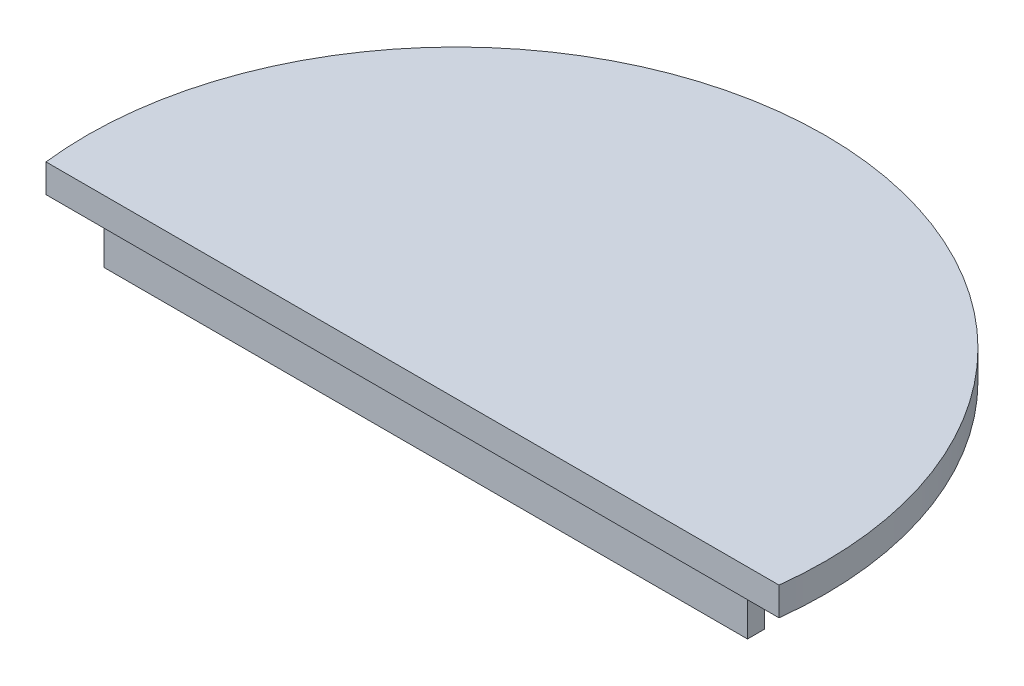
SolidWorks part; units mm, degrees
ref_plane "Front Plane" through (0, 0, 0) normal (0, 0, 1) x (1, 0, 0)
ref_plane "Top Plane" through (0, 0, 0) normal (0, 1, 0) x (1, 0, 0)
ref_plane "Right Plane" through (0, 0, 0) normal (1, 0, 0) x (0, 0, -1)
sketch "Sketch1" plane through (0, 0, 0) normal (0, 1, 0) x (1, 0, 0)
  line L0 (-123.3716, 0) -> (135.1744, 0) construction
  circle A0 centre (0, 0) radius 39
  dimension "D1" = 39
extrude "Boss-Extrude1" add sketch "Sketch1" along normal blind 3 contours A0
sketch "Sketch3" plane through (0, 3, 0) normal (0, 1, 0) x (1, 0, 0)
  line L1 (-54.8878, -4.6) -> (56.1007, -4.6)
  line L2 (-54.8878, -4.6) -> (-54.8878, -45.3292)
  line L3 (-54.8878, -45.3292) -> (56.1007, -45.3292)
  line L4 (56.1007, -4.6) -> (56.1007, -45.3292)
  dimension "D1" = 4.6
extrude "Cut-Extrude1" cut sketch "Sketch3" against normal blind 3 contours L1 L4 L3 L2
sketch "Sketch4" plane through (0, 0, 0) normal (0, -1, 0) x (1, 0, 0)
  line L0 (38.7278, 4.6) -> (-38.7278, 4.6) construction
  line L1 (-34, 3.2) -> (34, 3.2)
  line L2 (-34, 3.2) -> (-34, 1.4)
  line L3 (-34, 1.4) -> (34, 1.4)
  line L4 (34, 3.2) -> (34, 1.4)
  line L5 (0, 0) -> (0, 4.6) construction
  dimension "D1" = 1.8
  dimension "D2" = 1.4
  dimension "D3" = 68
extrude "Boss-Extrude2" add sketch "Sketch4" along normal blind 5
extrude "Boss-Extrude3" add sketch "Sketch4<2>" along normal blind 5
sketch "Sketch4<2>" plane through (0, 0, 0) normal (0, -1, 0) x (1, 0, 0) same geometry as "Sketch4"
